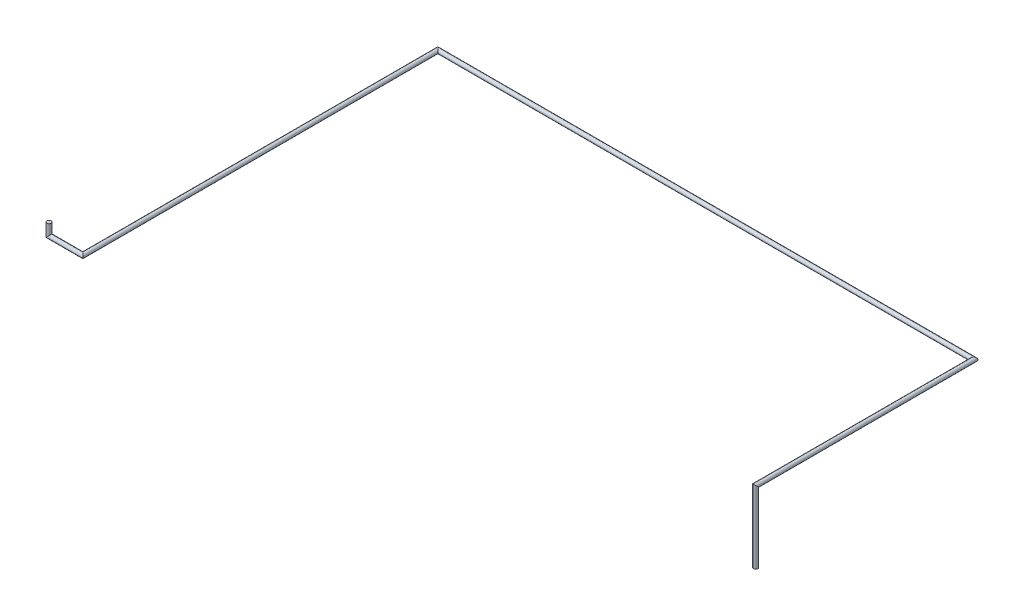
SolidWorks part; units mm, degrees
ref_plane "Alzado" through (0, 0, 0) normal (0, 0, 1) x (1, 0, 0)
ref_plane "Planta" through (0, 0, 0) normal (0, 1, 0) x (1, 0, 0)
ref_plane "Vista lateral" through (0, 0, 0) normal (1, 0, 0) x (0, 0, -1)
sketch "Croquis1" plane through (0, 0, 0) normal (0, 1, 0) x (1, 0, 0)
  circle A0 centre (0, 0) radius 12.7
  dimension "D1" = 25.4
extrude "Saliente-Extruir1" add sketch "Croquis1" along normal blind 20
sketch3d "Croquis3D1"
  line L0 (0, 20, 0) -> (0, 420, 0)
  line L1 (0, 20, 0) -> (0, 0, 0) construction
  line L2 (0, 420, 0) -> (0, 420, -1290)
  line L3 (0, 420, -1290) -> (-3170, 420, -1290)
  line L4 (-3170, 420, -1290) -> (-3170, 420, 810)
  line L5 (-3170, 420, 810) -> (-3370, 420, 810)
  line L6 (-3370, 420, 810) -> (-3370, 490, 810)
  dimension "D1" = 400
  dimension "D2" = 1290
  dimension "D3" = 3170
  dimension "D4" = 2100
  dimension "D5" = 200
  dimension "D6" = 70
sketch "Croquis2" plane through (0, 20, 0) normal (0, 1, 0) x (1, 0, 0)
  circle A0 centre (0, 0) radius 12.7
sweep "Barrer1" add profiles "Croquis2" path "Croquis3D1"
sketch "Croquis3" plane through (0, 0, 0) normal (0, -1, 0) x (1, 0, 0)
  line L1 (-0.6, 12.1) -> (0.6, 12.1)
  line L2 (-0.6, 12.1) -> (-0.6, 13.3)
  line L3 (-0.6, 13.3) -> (0.6, 13.3)
  line L4 (0.6, 12.1) -> (0.6, 13.3)
  line L5 (-0.6, 12.1) -> (0.6, 13.3) construction
  line L6 (-0.6, 13.3) -> (0.6, 12.1) construction
  circle A0 centre (0, 0) radius 12.7 construction
  point P0 (0, 12.7)
  dimension "D1" = 1.2
  dimension "D2" = 1.2
extrude "Saliente-Extruir2" add sketch "Croquis3" against normal blind 20
